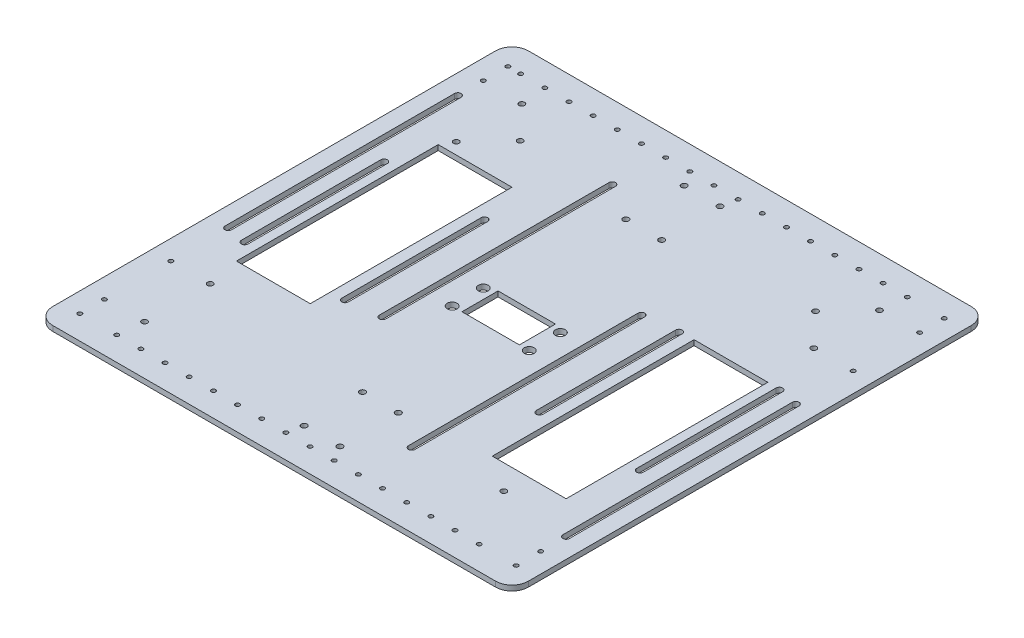
SolidWorks part; units mm, degrees
ref_plane "Front Plane" through (0, 0, 0) normal (0, 0, 1) x (1, 0, 0)
ref_plane "Top Plane" through (0, 0, 0) normal (0, 1, 0) x (1, 0, 0)
ref_plane "Right Plane" through (0, 0, 0) normal (1, 0, 0) x (0, 0, -1)
sketch "Sketch1" plane through (0, 0, 0) normal (0, 1, 0) x (1, 0, 0)
  line L0 (-145, 130.5) -> (145, 130.5) construction
  line L1 (145, -145) -> (-145, -145)
  line L2 (145, -145) -> (145, 145)
  line L3 (145, 145) -> (-145, 145)
  line L4 (-145, -145) -> (-145, 145)
  line L5 (145, -145) -> (-145, 145) construction
  line L6 (145, 145) -> (-145, -145) construction
  line L7 (-145, 116) -> (145, 116) construction
  line L8 (-145, 101.5) -> (145, 101.5) construction
  line L9 (-145, 87) -> (145, 87) construction
  line L10 (-145, 72.5) -> (145, 72.5) construction
  line L11 (-145, 58) -> (145, 58) construction
  line L12 (-145, 43.5) -> (145, 43.5) construction
  line L13 (-145, 29) -> (145, 29) construction
  line L14 (-145, 14.5) -> (145, 14.5) construction
  line L15 (-145, 0) -> (145, 0) construction
  line L16 (-145, -14.5) -> (145, -14.5) construction
  line L17 (-145, -29) -> (145, -29) construction
  line L18 (-145, -43.5) -> (145, -43.5) construction
  line L19 (-145, -58) -> (145, -58) construction
  line L20 (-145, -72.5) -> (145, -72.5) construction
  line L21 (-145, -87) -> (145, -87) construction
  line L22 (-145, -101.5) -> (145, -101.5) construction
  line L23 (-145, -116) -> (145, -116) construction
  line L24 (-145, -130.5) -> (145, -130.5) construction
  line L25 (-145, -145) -> (145, -145) construction
  point P0 (0, 0)
  dimension "D1" = 290
  dimension "D2" = 290
  dimension "D3" = 14.5
  dimension "D5" = 14.5
  dimension "D4" = 20
extrude "Base Plate" add sketch "Sketch1" along normal blind 3.175
hole_wizard "Caster Holes" positions "Sketch2" profile "Sketch3" hole size "M2" standard "ANSI Metric" end condition through all
sketch "Sketch2" plane through (0, 3.175, 0) normal (0, 1, 0) x (1, 0, 0)
  line L5 (0, -145) -> (0, 145) construction
  line L6 (145, 145) -> (-145, 145) construction
  line L8 (-145, 0) -> (145, 0) construction
  line L9 (-145, 0) -> (145, 0) construction
  line L10 (-145, 130.5) -> (145, 130.5) construction
  point P200 (-7.366, 130.5)
  point P217 (-22.098, 130.5)
  point P218 (-36.83, 130.5)
  point P219 (-51.562, 130.5)
  point P220 (-66.294, 130.5)
  point P221 (-81.026, 130.5)
  point P222 (-95.758, 130.5)
  point P223 (-110.49, 130.5)
  point P224 (110.49, 130.5)
  point P225 (95.758, 130.5)
  point P226 (81.026, 130.5)
  point P227 (66.294, 130.5)
  point P228 (51.562, 130.5)
  point P229 (36.83, 130.5)
  point P230 (22.098, 130.5)
  point P231 (7.366, 130.5)
  point P232 (7.366, -130.5)
  point P233 (22.098, -130.5)
  point P234 (36.83, -130.5)
  point P235 (51.562, -130.5)
  point P236 (66.294, -130.5)
  point P237 (81.026, -130.5)
  point P238 (95.758, -130.5)
  point P239 (110.49, -130.5)
  point P240 (-110.49, -130.5)
  point P241 (-95.758, -130.5)
  point P242 (-81.026, -130.5)
  point P243 (-66.294, -130.5)
  point P244 (-51.562, -130.5)
  point P245 (-36.83, -130.5)
  point P246 (-22.098, -130.5)
  point P247 (-7.366, -130.5)
  point P250 (-125.222, 130.5)
  dimension "D1" = 7.366
  dimension "D3" = 14.732
  dimension "D2" = 9
sketch "Sketch3" plane through (-125.222, 3.175, -130.5) normal (1, 0, 0) x (0, 0, 1)
  line L0 (0, 0) -> (0, 3.175)
  line L1 (0, 3.175) -> (1.3, 3.175)
  line L2 (1.3, 3.175) -> (1.3, 0)
  line L5 (1.3, 0) -> (0, 0)
  line L11 (0, -6.35) -> (0, 107.95) construction
  dimension "Thru Hole Dia." = 2.6
  dimension "Thru Hole Depth" = 3.175
fillet "Fillet1" radius 10 4 edges at (145, 1.5875, 145) (-145, 1.5875, 145) (145, 1.5875, -145) (-145, 1.5875, -145)
sketch "Sketch4" plane through (0, 0, 0) normal (0, -1, 0) x (1, 0, 0)
  line L0 (145, 0) -> (-145, 0) construction
  line L1 (-145, -135) -> (-145, 135) construction
  line L2 (0, -145) -> (0, 145) construction
  line L3 (-135, 145) -> (135, 145) construction
  point P6 (0, 0)
  point P12 (0, 0)
sketch "Sketch5" plane through (0, 3.175, 0) normal (0, 1, 0) x (1, 0, 0)
  line L0 (0, 145) -> (0, -145) construction
  line L1 (145, 0) -> (-145, 0) construction
  line L2 (0, 145) -> (0, -145) construction
  line L4 (-17.5, -13) -> (17.5, -13)
  line L5 (-17.5, -13) -> (-17.5, 9)
  line L6 (-17.5, 9) -> (17.5, 9)
  line L7 (17.5, -13) -> (17.5, 9)
  line L8 (-17.5, -13) -> (17.5, 9) construction
  line L9 (-17.5, 9) -> (17.5, -13) construction
  circle A0 centre (-23.5, 6) radius 3
  circle A2 centre (-23.5, -13) radius 3
  circle A3 centre (23.5, 6) radius 3
  circle A4 centre (23.5, -13) radius 3
  point P13 (0, -2)
  dimension "D1" = 6
  dimension "D2" = 23.5
  dimension "D3" = 6
  dimension "D4" = 19
  dimension "D5" = 6
  dimension "D6" = 6
extrude "Reflect Holes" cut sketch "Sketch5" against normal up to surface (3.175 mm away) up to face at (-7.366, 0, -129.2)
sketch "Sketch6" plane through (0, 3.175, 0) normal (0, 1, 0) x (1, 0, 0)
  line L0 (-133, 145) -> (-133, -145) construction
  line L1 (135, 145) -> (-135, 145) construction
  line L2 (-135, -145) -> (135, -145) construction
  line L3 (-145, 135) -> (-145, -135) construction
  line L4 (-133, 100) -> (-133, -40) construction
  line L5 (-131, 100) -> (-131, -40)
  line L6 (-135, 100) -> (-135, -40)
  line L7 (-38.9, 100) -> (-38.9, -40) construction
  line L8 (-36.9, 100) -> (-36.9, -40)
  line L9 (-40.9, 100) -> (-40.9, -40)
  line L10 (-120.5, 42.5) -> (-120.5, -42.5) construction
  line L11 (-118.5, 42.5) -> (-118.5, -42.5)
  line L12 (-122.5, 42.5) -> (-122.5, -42.5)
  line L13 (-59.3, 42.5) -> (-59.3, -42.5) construction
  line L14 (-57.3, 42.5) -> (-57.3, -42.5)
  line L15 (-61.3, 42.5) -> (-61.3, -42.5)
  line L16 (145, 0) -> (-145, 0) construction
  line L17 (0, -145) -> (0, 145) construction
  line L18 (38.9, 100) -> (38.9, -40) construction
  line L19 (36.9, 100) -> (36.9, -40) construction
  line L20 (40.9, 100) -> (40.9, -40) construction
  line L21 (59.3, 42.5) -> (59.3, -42.5) construction
  line L22 (57.3, 42.5) -> (57.3, -42.5)
  line L23 (61.3, 42.5) -> (61.3, -42.5)
  line L24 (120.5, 42.5) -> (120.5, -42.5) construction
  line L25 (118.5, 42.5) -> (118.5, -42.5)
  line L26 (122.5, 42.5) -> (122.5, -42.5)
  line L27 (133, 100) -> (133, -40) construction
  line L28 (131, 100) -> (131, -40) construction
  line L29 (135, 100) -> (135, -40) construction
  line L30 (133, -100) -> (133, 40) construction
  line L31 (131, -100) -> (131, 40)
  line L32 (135, -100) -> (135, 40)
  line L33 (38.9, -100) -> (38.9, 40) construction
  line L34 (36.9, -100) -> (36.9, 40)
  line L35 (40.9, -100) -> (40.9, 40)
  arc A0 (-131, 100) -> (-135, 100) centre (-133, 100) ccw
  arc A1 (-135, -40) -> (-131, -40) centre (-133, -40) ccw
  arc A4 (-36.9, 100) -> (-40.9, 100) centre (-38.9, 100) ccw
  arc A5 (-40.9, -40) -> (-36.9, -40) centre (-38.9, -40) ccw
  arc A6 (-118.5, 42.5) -> (-122.5, 42.5) centre (-120.5, 42.5) ccw
  arc A7 (-122.5, -42.5) -> (-118.5, -42.5) centre (-120.5, -42.5) ccw
  arc A8 (-57.3, 42.5) -> (-61.3, 42.5) centre (-59.3, 42.5) ccw
  arc A9 (-61.3, -42.5) -> (-57.3, -42.5) centre (-59.3, -42.5) ccw
  arc A10 (36.9, 100) -> (40.9, 100) centre (38.9, 100) cw construction
  arc A11 (40.9, -40) -> (36.9, -40) centre (38.9, -40) cw construction
  arc A12 (57.3, 42.5) -> (61.3, 42.5) centre (59.3, 42.5) cw
  arc A13 (61.3, -42.5) -> (57.3, -42.5) centre (59.3, -42.5) cw
  arc A14 (118.5, 42.5) -> (122.5, 42.5) centre (120.5, 42.5) cw
  arc A15 (122.5, -42.5) -> (118.5, -42.5) centre (120.5, -42.5) cw
  arc A16 (131, 100) -> (135, 100) centre (133, 100) cw construction
  arc A17 (135, -40) -> (131, -40) centre (133, -40) cw construction
  arc A18 (131, -100) -> (135, -100) centre (133, -100) ccw
  arc A19 (135, 40) -> (131, 40) centre (133, 40) ccw
  arc A20 (36.9, -100) -> (40.9, -100) centre (38.9, -100) ccw
  arc A21 (40.9, 40) -> (36.9, 40) centre (38.9, 40) ccw
  point P10 (-133, 30)
  point P15 (-38.9, 30)
  point P27 (-120.5, 0)
  point P34 (-59.3, 0)
  point P44 (0, 0)
  point P46 (0, 0)
  point P48 (38.9, 30)
  point P55 (59.3, 0)
  point P62 (120.5, 0)
  point P69 (133, 30)
  point P76 (133, -30)
  point P83 (38.9, -30)
  dimension "D3" = 2
  dimension "D6" = 2
  dimension "D1" = 12
  dimension "D2" = 140
  dimension "D4" = 94.1
  dimension "D5" = 12.5
  dimension "D7" = 85
  dimension "D8" = 61.2
  dimension "D9" = 45
extrude "bearing slots" cut sketch "Sketch6" against normal up to surface (3.175 mm away) up to face at (23.5, 0, -3)
sketch "Sketch7" plane through (0, 3.175, 0) normal (0, 1, 0) x (1, 0, 0)
  line L0 (-145, 135) -> (-145, -135) construction
  line L9 (-113, 43) -> (-68, 43)
  line L10 (-113, 43) -> (-113, -55)
  line L11 (-113, -55) -> (-68, -55)
  line L12 (-68, 43) -> (-68, -55)
  point P9 (-68, -6)
  dimension "D2" = 98
  dimension "D1" = 45
  dimension "D3" = 32
  dimension "D4" = 6
extrude "wheel slots" cut sketch "Sketch7" against normal up to surface (3.175 mm away) up to face at (-133, 0, -30)
mirror "Mirror2" about plane through (0, 0, 0) normal (1, 0, 0) of "wheel slots"
sketch "Sketch9" plane through (0, 3.175, 0) normal (0, 1, 0) x (1, 0, 0)
  line L0 (-109, -145) -> (-109, 145) construction
  line L1 (135, 145) -> (-135, 145) construction
  line L2 (-145, 135) -> (-145, -135) construction
  line L3 (-135, -145) -> (135, -145) construction
  line L4 (90, -145) -> (90, 145) construction
  line L5 (145, -135) -> (145, 135) construction
  point P0 (-109, -75)
  point P1 (-109, -115)
  point P2 (90, -95)
  point P8 (-109, 0)
  point P21 (90, 0)
  dimension "D1" = 36
  dimension "D2" = 70
  dimension "D3" = 30
  dimension "D4" = 55
  dimension "D5" = 50
hole_wizard "standoff holes" positions "Sketch10" profile "Sketch11" hole size "M3" standard "ANSI Metric" end condition through all
sketch "Sketch10" plane through (0, 3.175, 0) normal (0, 1, 0) x (1, 0, 0)
  line L0 (145, 0) -> (-145, 0) construction
  line L1 (-145, 135) -> (-145, -135) construction
  line L2 (0, -145) -> (0, 145) construction
  line L3 (135, 145) -> (-135, 145) construction
  line L4 (145, -145) -> (-145, 145) construction
  point P0 (-109, -75)
  point P3 (-109, -115)
  point P6 (90, -95)
  point P56 (0, 0)
  point P105 (0, 0)
  point P230 (0, 0)
  point P231 (90, 95)
  point P232 (-109, 115)
  point P233 (-109, 75)
  point P235 (-90, 95)
  point P236 (109, 75)
  point P237 (109, 115)
  dimension "D1" = 45
sketch "Sketch11" plane through (-109, 3.175, 75) normal (1, 0, 0) x (0, 0, 1)
  line L0 (0, 0) -> (0, 3.175)
  line L1 (0, 3.175) -> (1.7, 3.175)
  line L2 (1.7, 3.175) -> (1.7, 0)
  line L5 (1.7, 0) -> (0, 0)
  line L11 (0, -6.35) -> (0, 107.95) construction
  dimension "Thru Hole Dia." = 3.4
  dimension "Thru Hole Depth" = 3.175
sketch "Sketch12" plane through (0, 3.175, 0) normal (0, 1, 0) x (1, 0, 0)
  line L10 (-68, 43) -> (-68, -55) construction
  line L11 (-113, 43) -> (-68, 43)
  line L12 (-113, 43) -> (-113, 68)
  line L13 (-113, 68) -> (-68, 68)
  line L14 (-68, 43) -> (-68, 68)
  line L15 (68, -55) -> (113, -55)
  line L16 (68, -55) -> (68, -80)
  line L17 (68, -80) -> (113, -80)
  line L18 (113, -55) -> (113, -80)
  line L19 (113, 43) -> (113, -55) construction
  dimension "D1" = 25
  dimension "D2" = 25
extrude "wheel holes" cut sketch "Sketch12" against normal up to surface (3.175 mm away) up to face at (-109, 0, 76.7)
sketch "Sketch13" plane through (0, 3.175, 0) normal (0, 1, 0) x (1, 0, 0)
  line L0 (0, -145) -> (0, 145) construction
  line L7 (135, 145) -> (-135, 145) construction
  line L8 (19.75, -103.53) -> (-8.75, -103.53) construction
  line L9 (-8.75, -82.38) -> (19.75, -82.38) construction
  line L10 (-8.75, -82.38) -> (-8.75, -124.68) construction
  line L11 (-8.75, -124.68) -> (19.75, -124.68) construction
  line L12 (19.75, -82.38) -> (19.75, -124.68) construction
  line L13 (-8.75, -82.38) -> (19.75, -124.68) construction
  line L14 (-8.75, -124.68) -> (19.75, -82.38) construction
  line L15 (5.5, -124.68) -> (5.5, -82.38) construction
  line L16 (-135, -145) -> (135, -145) construction
  line L17 (145, 0) -> (-145, 0) construction
  line L18 (-145, 135) -> (-145, -135) construction
  line L19 (16.42, -121.312) -> (16.42, -145) construction
  line L20 (-16.34, 121.312) -> (-16.34, 145) construction
  line L21 (0, 121.312) -> (5.5, 121.312) construction
  circle A4 centre (16.42, -85.748) radius 1.75
  circle A6 centre (16.42, -121.312) radius 1.75
  circle A7 centre (-5.42, -121.312) radius 1.75
  circle A8 centre (-5.42, -85.748) radius 1.75
  circle A9 centre (5.5, 85.748) radius 1.75
  circle A10 centre (-16.34, 85.748) radius 1.75
  circle A11 centre (-16.34, 121.312) radius 1.75
  circle A12 centre (5.5, 121.312) radius 1.75
  point P12 (0, 0)
  point P22 (5.5, -103.53)
  point P24 (5.5, -103.53)
  point P30 (5.5, -103.53)
  point P32 (0, 0)
  point P44 (0.04, 0)
  dimension "D1" = 20.32
  dimension "D2" = 3.5
  dimension "D3" = 2
  dimension "D4" = 5.5
  dimension "D5" = 5.5
  dimension "D6" = 28.5
  dimension "D7" = 42.3
  dimension "D8" = 3.368
  dimension "D9" = 3.33
extrude "Cut-Extrude1" cut sketch "Sketch13" against normal up to surface (3.175 mm away) up to face at (90.5, 0, 18.5)
sketch "Sketch14" plane through (0, 3.175, 0) normal (0, 1, 0) x (1, 0, 0)
  line L0 (133, 145) -> (133, -145) construction
  line L1 (135, 145) -> (-135, 145) construction
  line L2 (-135, -145) -> (135, -145) construction
  line L3 (-133, -145) -> (-133, 145) construction
  arc A0 (135, 40) -> (131, 40) centre (133, 40) ccw construction
  circle A1 centre (110.49, 130.5) radius 1.3 construction
  circle A2 centre (110.49, 130.5) radius 1.3 construction
  circle A3 centre (109, 75) radius 1.7 construction
  circle A4 centre (109, 75) radius 1.7 construction
  circle A5 centre (110.49, -130.5) radius 1.3 construction
  circle A6 centre (110.49, -130.5) radius 1.3 construction
  arc A7 (-131, 100) -> (-135, 100) centre (-133, 100) ccw construction
  point P0 (133, 130.5)
  point P1 (133, 115.5)
  point P2 (133, 75)
  point P3 (133, -115.5)
  point P4 (133, -130.5)
  point P14 (133, 42)
  point P15 (-133, -130.5)
  point P18 (-133, -115.5)
  point P19 (-133, -75)
  point P23 (-133, 115.5)
  point P24 (-133, 130.5)
  point P28 (0, 0)
  point P35 (-133, 102)
  dimension "D1" = 15
  dimension "D2" = 15
  dimension "D3" = 2
hole_wizard "wall holes" positions "Sketch15" profile "Sketch16" hole size "M2" standard "ANSI Metric" end condition through all
sketch "Sketch15" plane through (0, 3.175, 0) normal (0, 1, 0) x (1, 0, 0)
  point P0 (-133, -130.5)
  point P3 (-133, -115.5)
  point P6 (-133, -75)
  point P9 (-133, 115.5)
  point P12 (-133, 130.5)
  point P15 (133, 130.5)
  point P18 (133, 115.5)
  point P21 (133, 75)
  point P24 (133, -115.5)
  point P27 (133, -130.5)
sketch "Sketch16" plane through (-133, 3.175, 130.5) normal (1, 0, 0) x (0, 0, 1)
  line L0 (0, 0) -> (0, 3.175)
  line L1 (0, 3.175) -> (1.3, 3.175)
  line L2 (1.3, 3.175) -> (1.3, 0)
  line L5 (1.3, 0) -> (0, 0)
  line L11 (0, -6.35) -> (0, 107.95) construction
  dimension "Thru Hole Dia." = 2.6
  dimension "Thru Hole Depth" = 3.175
